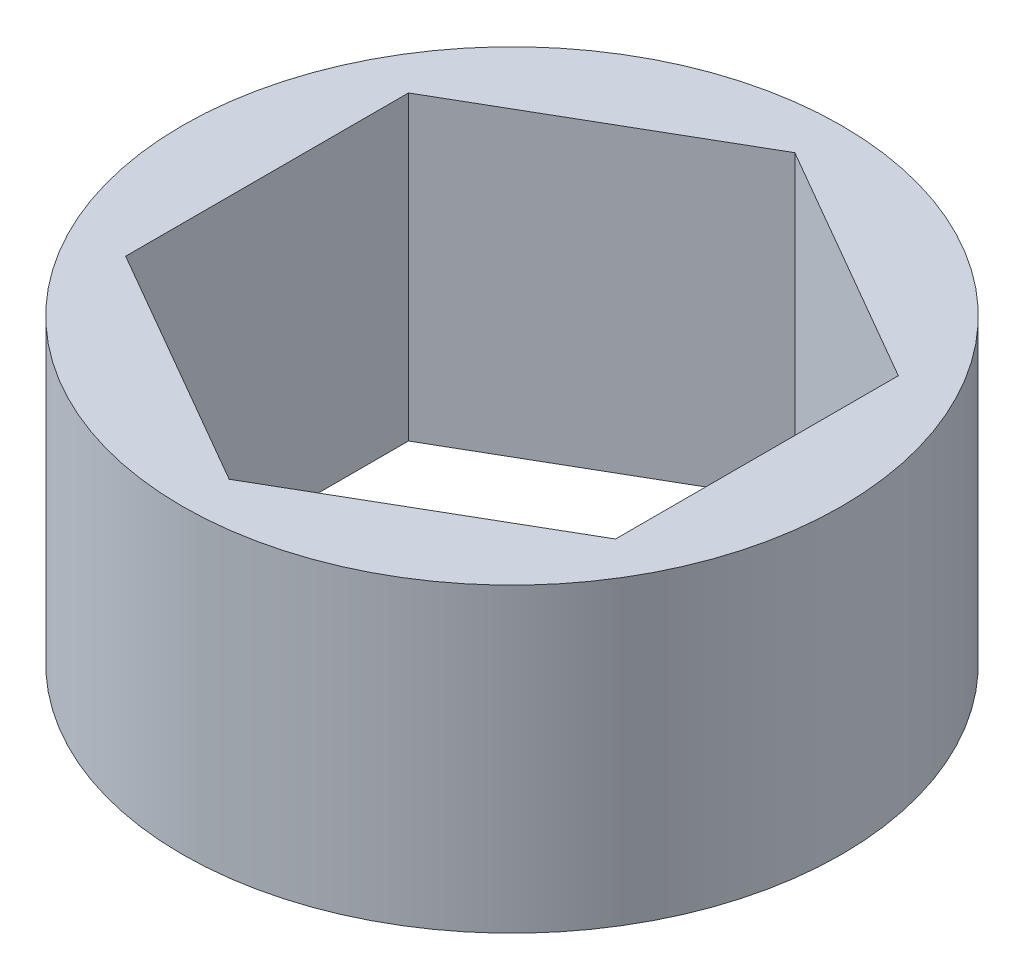
SolidWorks part; units mm, degrees
material "PET"
ref_plane "Front Plane" through (0, 0, 0) normal (0, 0, 1) x (1, 0, 0)
ref_plane "Top Plane" through (0, 0, 0) normal (0, 1, 0) x (1, 0, 0)
ref_plane "Right Plane" through (0, 0, 0) normal (1, 0, 0) x (0, 0, -1)
sketch "Sketch1" plane through (0, 0, 0) normal (0, 1, 0) x (1, 0, 0)
  line L1 (0, 7.6256) -> (-6.604, 3.8128)
  line L2 (-6.604, 3.8128) -> (-6.604, -3.8128)
  line L3 (-6.604, -3.8128) -> (0, -7.6256)
  line L4 (0, -7.6256) -> (6.604, -3.8128)
  line L5 (6.604, -3.8128) -> (6.604, 3.8128)
  line L6 (6.604, 3.8128) -> (0, 7.6256)
  circle A0 centre (0, 0) radius 8.89
  circle A2 centre (0, 0) radius 6.604 construction
  dimension "D1" = 13.208
  dimension "D2" = 17.78
extrude "Boss-Extrude1" add sketch "Sketch1" along normal mid plane 8.128
